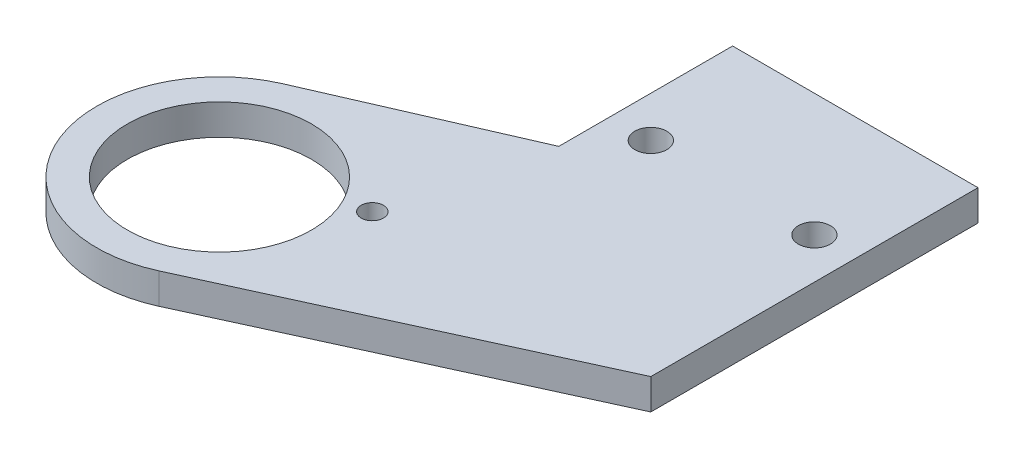
SolidWorks part; units mm, degrees
ref_plane "Front Plane" through (0, 0, 0) normal (0, 0, 1) x (1, 0, 0)
ref_plane "Top Plane" through (0, 0, 0) normal (0, 1, 0) x (1, 0, 0)
ref_plane "Right Plane" through (0, 0, 0) normal (1, 0, 0) x (0, 0, -1)
sketch "Sketch2" plane through (0, 0, 0) normal (0, 1, 0) x (1, 0, 0)
  line L0 (19.05, 0) -> (-19.05, 0)
  line L1 (-19.05, 0) -> (-19.05, -26.9875)
  line L2 (-19.05, -26.9875) -> (-48.884, -39.9857)
  line L3 (19.05, 0) -> (19.05, -50.8)
  line L4 (-33.3415, -74.7695) -> (19.05, -50.8)
  circle A0 centre (-41.275, -57.4501) radius 14.2875
  arc A2 (-48.884, -39.9857) -> (-33.3415, -74.7695) centre (-41.275, -57.4501) ccw
extrude "Boss-Extrude1" add sketch "Sketch2" along normal blind 4.7625
sketch "Sketch3" plane through (0, 4.7625, 0) normal (0, 1, 0) x (1, 0, 0)
  line L0 (-41.275, -57.4501) -> (-24.742, -50.2469) construction
  line L1 (0, 0) -> (0, -19.05) construction
  line L2 (0, -19.05) -> (12.7, -19.05) construction
  line L3 (0, -19.05) -> (-12.7, -19.05) construction
  point P8 (0, 0)
  dimension "D1" = 25.4
hole_wizard "Tap Drill for #8-32 Tap1" positions "Sketch4" profile "Sketch5" hole size "#8-32" standard "ANSI Inch" end condition through all
sketch "Sketch4" plane through (0, 4.7625, 0) normal (0, 1, 0) x (1, 0, 0)
  point P0 (-24.742, -50.2469)
sketch "Sketch5" plane through (-24.742, 4.7625, 50.2469) normal (1, 0, 0) x (0, 0, 1)
  line L0 (0, 0) -> (0, 4.7625)
  line L1 (0, 4.7625) -> (1.7272, 4.7625)
  line L2 (1.7272, 4.7625) -> (1.7272, 0)
  line L5 (1.7272, 0) -> (0, 0)
  line L11 (0, -6.35) -> (0, 107.95) construction
  dimension "Thru Hole Dia." = 3.4544
  dimension "Thru Hole Depth" = 4.7625
hole_wizard "#10 Clearance Hole1" positions "Sketch6" profile "Sketch7" hole size "#10" standard "ANSI Inch" end condition through all
sketch "Sketch6" plane through (0, 4.7625, 0) normal (0, 1, 0) x (1, 0, 0)
  point P0 (-12.7, -19.05)
  point P3 (12.7, -19.05)
sketch "Sketch7" plane through (-12.7, 4.7625, 19.05) normal (1, 0, 0) x (0, 0, 1)
  line L0 (0, 0) -> (0, 4.7625)
  line L1 (0, 4.7625) -> (2.4892, 4.7625)
  line L2 (2.4892, 4.7625) -> (2.4892, 0)
  line L5 (2.4892, 0) -> (0, 0)
  line L11 (0, -6.35) -> (0, 107.95) construction
  dimension "Thru Hole Dia." = 4.9784
  dimension "Thru Hole Depth" = 4.7625
